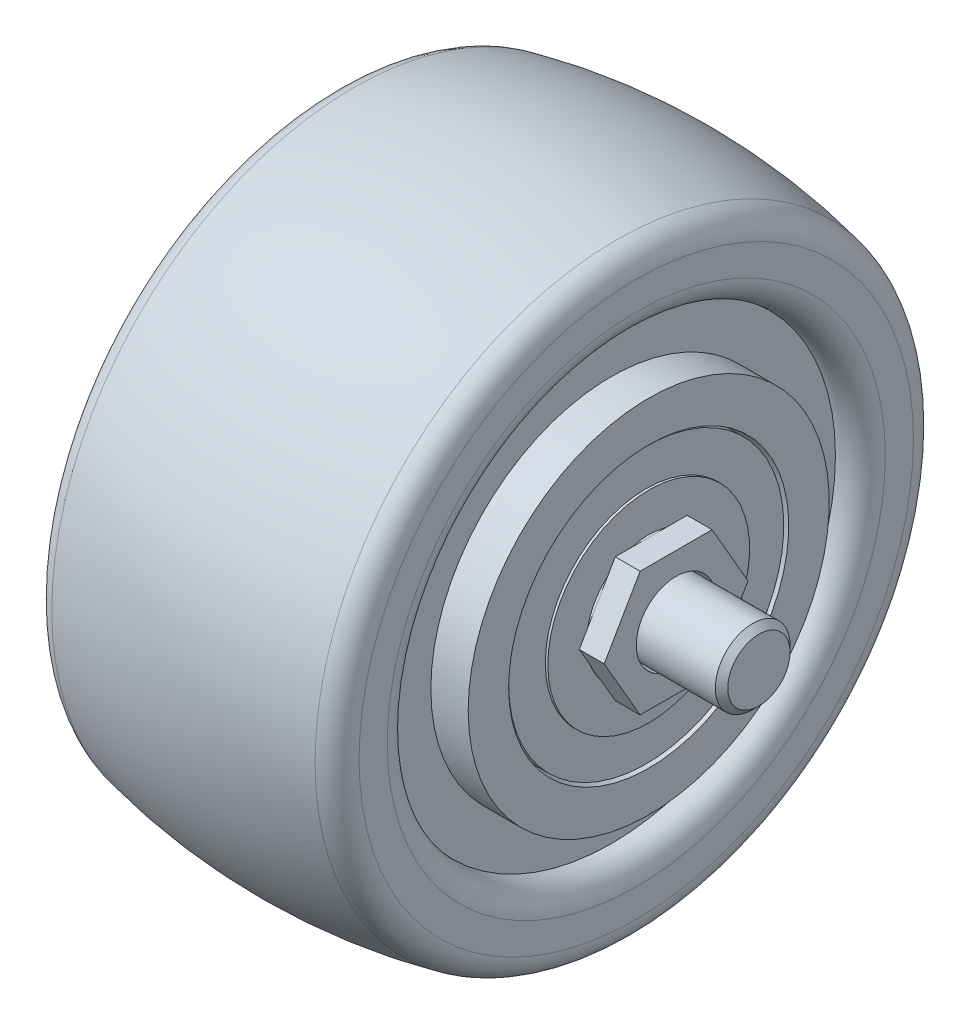
SolidWorks part; units mm, degrees
ref_plane "Front Plane" through (0, 0, 0) normal (0, 0, 1) x (1, 0, 0)
ref_plane "Top Plane" through (0, 0, 0) normal (0, 1, 0) x (1, 0, 0)
ref_plane "Right Plane" through (0, 0, 0) normal (1, 0, 0) x (0, 0, -1)
sketch "Sketch1" plane through (0, 0, 0) normal (1, 0, 0) x (0, 0, -1)
  circle A0 centre (0, 0) radius 25.35
  dimension "D1" = 50.7
extrude "Boss-Extrude1" add sketch "Sketch1" along normal blind 12.15 and the other way blind 12.15
sketch "Sketch2" plane through (0, 0, 0) normal (0, 0, 1) x (1, 0, 0)
  line L0 (0, 0) -> (-48.3586, 0) construction
  line L1 (0, 0) -> (0, -24.65) construction
  line L2 (12.15, 25.35) -> (-12.15, 25.35) construction
  line L4 (15.995, 22.7226) -> (16.3985, 22.7226)
  line L5 (0, 25.35) -> (-8.1733, 25.35) construction
  line L6 (-15.995, 22.7226) -> (-15.995, 31.6473)
  line L7 (-15.995, 31.6473) -> (16.3985, 31.6473)
  line L8 (16.3985, 22.7226) -> (16.3985, 31.6473)
  arc A0 (15.995, 22.7226) -> (-15.995, 22.7226) centre (0, -24.65) ccw
  dimension "D1" = 100
revolve "Cut-Revolve1" cut sketch "Sketch2" angle 360 about L0
fillet "Fillet1" radius 2 2 edges at (-12.15, 0, -23.8513) (12.15, 0, -23.8513)
sketch "Sketch3" plane through (-12.15, 0, 0) normal (-1, 0, 0) x (0, 0, 1)
  circle A0 centre (0, 0) radius 18
  dimension "D1" = 36
extrude "Cut-Extrude1" cut sketch "Sketch3" against normal blind 2
mirror "Mirror1" about plane through (0, 0, 0) normal (1, 0, 0) of "Cut-Extrude1"
fillet "Fillet2" radius 2 2 edges at (-12.15, 0, 18) (12.15, 0, 18)
sketch "Sketch4" plane through (-10.15, 0, 0) normal (-1, 0, 0) x (0, 0, 1)
  circle A0 centre (0, 0) radius 14.5
  dimension "D1" = 29
extrude "Boss-Extrude2" add sketch "Sketch4" along normal blind 3
mirror "Mirror2" about plane through (0, 0, 0) normal (1, 0, 0) of "Boss-Extrude2"
sketch "Sketch5" plane through (-13.15, 0, 0) normal (-1, 0, 0) x (0, 0, 1)
  circle A0 centre (0, 0) radius 11.25
  dimension "D1" = 22.5
extrude "Cut-Extrude2" cut sketch "Sketch5" against normal blind 3
sketch "Sketch6" plane through (-10.15, 0, 0) normal (-1, 0, 0) x (0, 0, 1)
  circle A2 centre (0, 0) radius 11.05
  circle A3 centre (0, 0) radius 11.05
  dimension "D1" = 0.2
extrude "Boss-Extrude3" add sketch "Sketch6" along normal blind 2.8
sketch "Sketch7" plane through (-12.95, 0, 0) normal (-1, 0, 0) x (0, 0, 1)
  circle A0 centre (0, 0) radius 8.1034
extrude "Boss-Extrude4" add sketch "Sketch7" along normal blind 0.2
mirror "Mirror4" about plane through (0, 0, 0) normal (1, 0, 0) of "Boss-Extrude4", "Boss-Extrude3", "Cut-Extrude2"
sketch "Sketch8" plane through (0, 0, 0) normal (1, 0, 0) x (0, 0, -1)
  circle A0 centre (0, 0) radius 3
  dimension "D1" = 6
extrude "Boss-Extrude5" add sketch "Sketch8" along normal blind 22 and the other way blind 22
chamfer "Chamfer1" distance 0.5 angle 45 2 edges at (22, 0, -3) (-22, 0, -3)
sketch "Sketch9" plane through (-13.15, 0, 0) normal (-1, 0, 0) x (0, 0, 1)
  circle A0 centre (0, 0) radius 5
  circle A1 centre (0, 0) radius 3
  dimension "D1" = 10
extrude "Boss-Extrude6" add sketch "Sketch9" along normal blind 0.2
mirror "Mirror5" about plane through (0, 0, 0) normal (1, 0, 0) of "Boss-Extrude6"
sketch "Sketch10" plane through (13.35, 0, 0) normal (1, 0, 0) x (0, 0, -1)
  line L1 (5.7735, 0) -> (2.8868, 5)
  line L2 (2.8868, 5) -> (-2.8868, 5)
  line L3 (-2.8868, 5) -> (-5.7735, 0)
  line L4 (-5.7735, 0) -> (-2.8868, -5)
  line L5 (-2.8868, -5) -> (2.8868, -5)
  line L6 (2.8868, -5) -> (5.7735, 0)
  circle A0 centre (0, 0) radius 5 construction
  circle A1 centre (0, 0) radius 3.2
  dimension "D2" = 6.4
  dimension "D1" = 10
extrude "Boss-Extrude7" add sketch "Sketch10" along normal blind 2
mirror "Mirror6" about plane through (0, 0, 0) normal (1, 0, 0) of "Boss-Extrude7"
sketch "Sketch11" plane through (10.15, 0, 0) normal (1, 0, 0) x (0, 0, -1)
  circle A0 centre (0.8511, -15.9773) radius 0.75
  circle A1 centre (0, 0) radius 14.5 construction
  circle A2 centre (0, 0) radius 14.5 construction
  dimension "D1" = 16
  dimension "D2" = 1.5
  dimension "D3" = 0.8511
extrude "Cut-Extrude3" cut sketch "Sketch11" against normal through all
